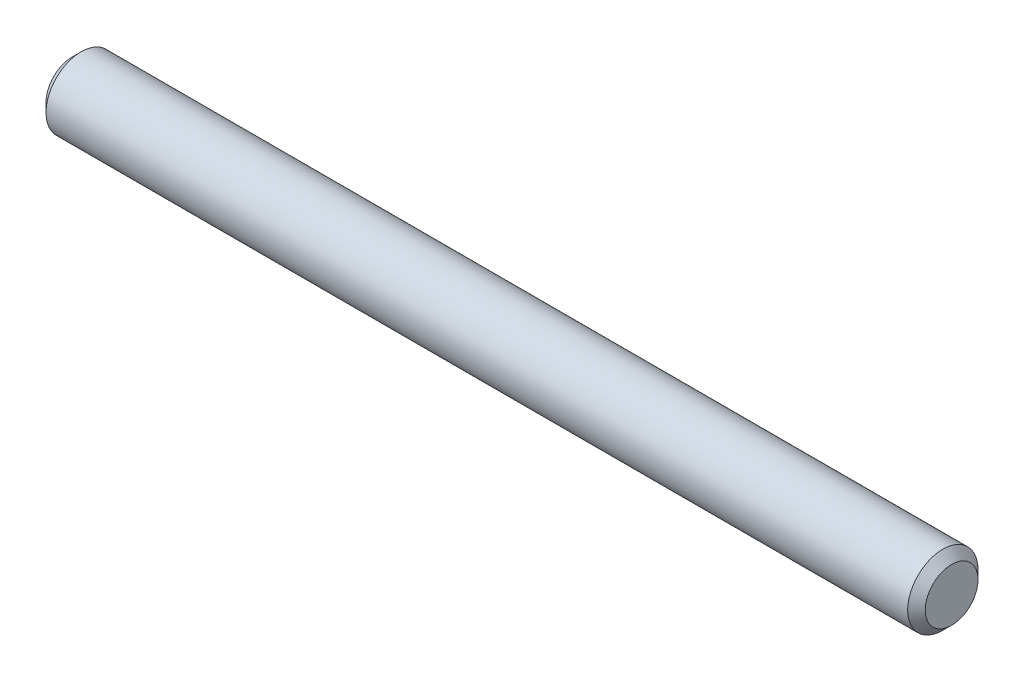
SolidWorks part; units mm, degrees
material "Stainless Steel (ferritic)"
ref_plane "Front Plane" through (0, 0, 0) normal (0, 0, 1) x (1, 0, 0)
ref_plane "Top Plane" through (0, 0, 0) normal (0, 1, 0) x (1, 0, 0)
ref_plane "Right Plane" through (0, 0, 0) normal (1, 0, 0) x (0, 0, -1)
sketch "Sketch1" plane through (0, 0, 0) normal (1, 0, 0) x (0, 0, -1)
  circle A0 centre (0, 0) radius 2
  dimension "D1" = 4
extrude "Boss-Extrude1" add sketch "Sketch1" along normal mid plane 50
chamfer "Chamfer1" distance 0.5 angle 45 2 edges at (-25, 0, -2) (25, 0, -2)
ref_axis "Axis1" through (24.5, 0, 0) along (-1, 0, 0)
